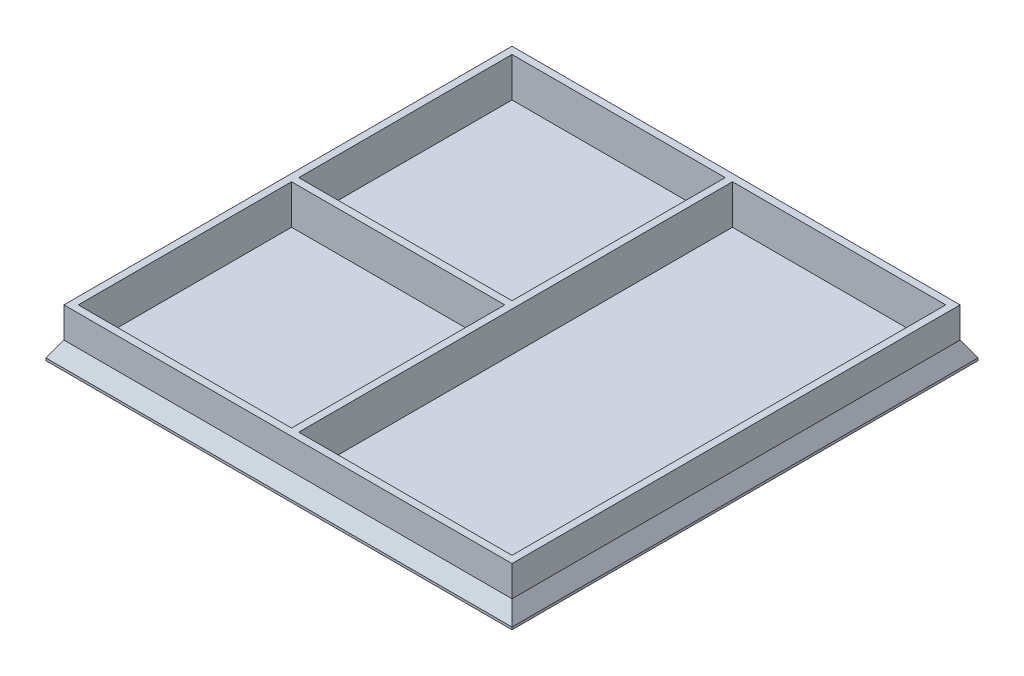
SolidWorks part; units mm, degrees
ref_plane "Přední rovina" through (0, 0, 0) normal (0, 0, 1) x (1, 0, 0)
ref_plane "Horní rovina" through (0, 0, 0) normal (0, 1, 0) x (1, 0, 0)
ref_plane "Pravá rovina" through (0, 0, 0) normal (1, 0, 0) x (0, 0, -1)
sketch "Skica1" plane through (0, 0, 0) normal (0, 1, 0) x (1, 0, 0)
  line L0 (-104, 104) -> (0, 0) construction
  line L1 (0, 0) -> (-104, 0)
  line L2 (0, 0) -> (0, 104)
  line L3 (0, 104) -> (-104, 104)
  line L4 (-104, 0) -> (-104, 104)
  line L5 (-104, 0) -> (0, 104) construction
  line L6 (-52, 102) -> (-52, 2) construction
  line L7 (-102, 102) -> (-2, 102)
  line L8 (-102, 102) -> (-102, 2)
  line L9 (-102, 2) -> (-2, 2)
  line L10 (-2, 102) -> (-2, 2)
  line L11 (-102, 102) -> (-2, 2) construction
  line L12 (-102, 2) -> (-2, 102) construction
  line L13 (-102, 52) -> (-2, 52) construction
  line L15 (-51.2, 100.4) -> (-3.6, 100.4)
  line L16 (-51.2, 100.4) -> (-51.2, 3.6)
  line L17 (-51.2, 3.6) -> (-3.6, 3.6)
  line L18 (-3.6, 100.4) -> (-3.6, 3.6)
  line L19 (-100.4, 100.4) -> (-52.8, 100.4)
  line L20 (-100.4, 100.4) -> (-100.4, 52.8)
  line L21 (-100.4, 52.8) -> (-52.8, 52.8)
  line L22 (-52.8, 100.4) -> (-52.8, 52.8)
  line L23 (-100.4, 51.2) -> (-52.8, 51.2)
  line L24 (-100.4, 51.2) -> (-100.4, 3.6)
  line L25 (-100.4, 3.6) -> (-52.8, 3.6)
  line L26 (-52.8, 51.2) -> (-52.8, 3.6)
  point P4 (-52, 52)
  point P26 (0, 0)
  dimension "D1" = 104
  dimension "D2" = 104
  dimension "D3" = 100
  dimension "D4" = 100
  dimension "D5" = 1.6
  dimension "D6" = 1.6
  dimension "D7" = 0.8
  dimension "D8" = 1.6
  dimension "D9" = 1.6
  dimension "D10" = 1.6
  dimension "D11" = 0.8
  dimension "D12" = 0.8
  dimension "D13" = 1.6
  dimension "D14" = 0.8
  dimension "D15" = 1.6
  dimension "D16" = 0.8
extrude "Přidat vysunutím1" add sketch "Skica1" along normal blind 2 contours L3 L4 L1 L2
extrude "Přidat vysunutím2" add sketch "Skica1<3>" along normal blind 10.8 contours L10 L7 L8 L9 L15 L18 L17 L16 L19 L22 L21 L20 L23 L26 L25 L24 region at (-54.1765, 0, -52)
sketch "Skica1<3>" plane through (0, 0, 0) normal (0, 1, 0) x (1, 0, 0) same geometry as "Skica1"
extrude "Přidat vysunutím3" add sketch "Skica1<4>" along normal blind 4 contours L4 L1 L2 L3 L7 L10 L9 L8 region at (-52, 0, -1.4708)
sketch "Skica1<4>" plane through (0, 0, 0) normal (0, 1, 0) x (1, 0, 0) same geometry as "Skica1"
chamfer "Zkosení2" distance 2 angle 60 4 edges at (-104, 4, -52) (-52, 4, -104) (0, 4, -52) (-52, 4, 0) first distance on face at (-52, 4, -52)
